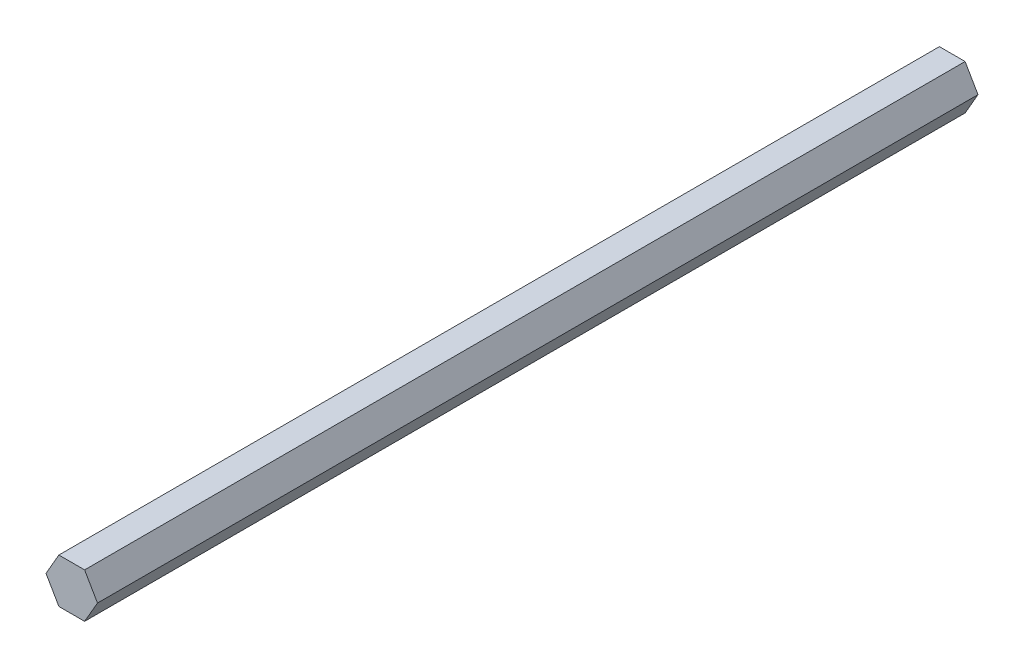
SolidWorks part; units mm, degrees
ref_plane "Front Plane" through (0, 0, 0) normal (0, 0, 1) x (1, 0, 0)
ref_plane "Top Plane" through (0, 0, 0) normal (0, 1, 0) x (1, 0, 0)
ref_plane "Right Plane" through (0, 0, 0) normal (1, 0, 0) x (0, 0, -1)
sketch "Sketch1" plane through (0, 0, 0) normal (0, 0, 1) x (1, 0, 0)
  line L1 (-7.3323, 0) -> (-3.6662, -6.35)
  line L2 (-3.6662, -6.35) -> (3.6662, -6.35)
  line L3 (3.6662, -6.35) -> (7.3323, 0)
  line L4 (7.3323, 0) -> (3.6662, 6.35)
  line L5 (3.6662, 6.35) -> (-3.6662, 6.35)
  line L6 (-3.6662, 6.35) -> (-7.3323, 0)
  circle A0 centre (0, 0) radius 6.35 construction
  dimension "D1" = 12.7
extrude "Boss-Extrude1" add sketch "Sketch1" along normal blind 250.825
